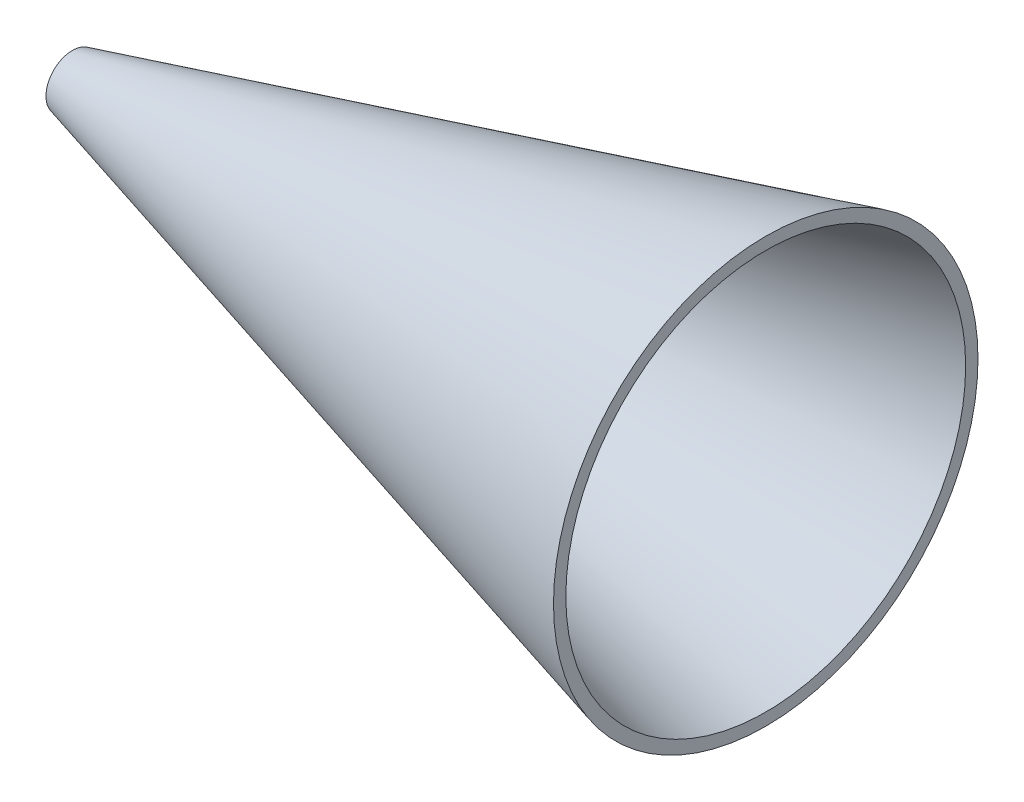
SolidWorks part; units mm, degrees
material "C (Grafite)"
ref_plane "Piano frontale" through (0, 0, 0) normal (0, 0, 1) x (1, 0, 0)
ref_plane "Piano superiore" through (0, 0, 0) normal (0, 1, 0) x (1, 0, 0)
ref_plane "Piano destro" through (0, 0, 0) normal (1, 0, 0) x (0, 0, -1)
sketch "Schizzo1" plane through (0, 0, 0) normal (0, 0, 1) x (1, 0, 0)
  line L0 (-13.835, 5.9) -> (277.165, 83.9)
  line L1 (-77.4018, 0) -> (77.4018, 0) construction
  line L2 (-13.835, 11.0765) -> (277.165, 89.0765)
  line L3 (-13.835, 5.9) -> (-13.835, 11.0765)
  line L4 (277.165, 89.0765) -> (277.165, 83.9)
  dimension "D1" = 5.9
  dimension "D2" = 83.9
  dimension "D3" = 291
  dimension "D4" = 5
revolve "Rivoluzione1" add sketch "Schizzo1" angle 360 about L1
